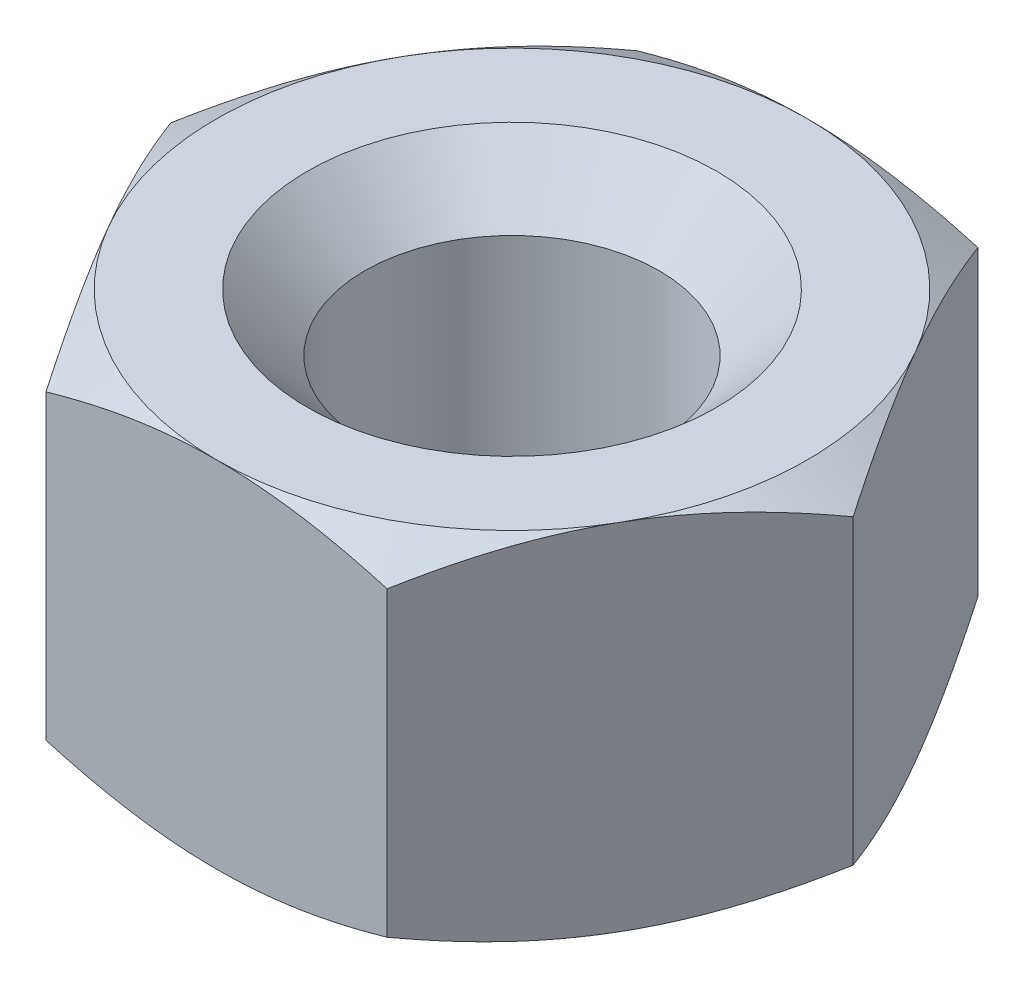
SolidWorks part; units mm, degrees
ref_plane "Plan1" through (0, 0, 0) normal (0, 0, 1) x (1, 0, 0)
ref_plane "Plan2" through (0, 0, 0) normal (0, 1, 0) x (1, 0, 0)
ref_plane "Plan3" through (0, 0, 0) normal (1, 0, 0) x (0, 0, -1)
sketch "Esquisse1" plane through (0, 0, 0) normal (0, 0, 1) x (1, 0, 0)
  line L1 (4.4845, 10.8) -> (9, 10.8)
  line L2 (9, 10.8) -> (12.7279, 8.6477)
  line L3 (12.7279, 8.6477) -> (12.7279, 2.1523)
  line L4 (12.7279, 2.1523) -> (9, 0)
  line L5 (9, 0) -> (4.4845, 0)
  line L6 (0, 2.4) -> (0, 0) construction
  line L7 (4.4845, 0) -> (4.4845, 10.8)
  line L8 (-2.75, 0) -> (15.25, 0) construction
  line L9 (-1.5155, 0) -> (10.4845, 0) construction
  dimension "D1" = 12.7279
  dimension "Hauteur" = 10.8
  dimension "D2" = 30
  dimension "D4" = 9
  dimension "D5" = 30
  dimension "D6" = 4.4845
  dimension "Cote sur plats" = 18
  dimension "Diamètre nominal" = 12
revolve "Base-Révolution" add sketch "Esquisse1" angle 360 about L6
sketch "Esquisse2" plane through (0, 0, 0) normal (0, 1, 0) x (1, 0, 0)
  line L0 (0, 2.4733) -> (0, -2.457) construction
  line L1 (0, 0) -> (1.6745, -2.9003) construction
  line L2 (-5.1962, -9) -> (5.1962, -9)
  line L3 (0, 0) -> (2.3797, -1.3739) construction
  line L4 (5.1962, -9) -> (10.3923, 0)
  line L5 (0, 0) -> (2.9763, 0) construction
  line L6 (5.1962, 9) -> (10.3923, 0)
  line L7 (-5.1962, 9) -> (5.1962, 9)
  line L8 (-5.1962, 9) -> (-10.3923, 0)
  line L9 (-5.1962, -9) -> (-10.3923, 0)
  circle A0 centre (0, 0) radius 9 construction
  point P14 (0, 9)
  point P16 (0, -9)
  dimension "D1" = 30
  dimension "D2" = 30
extrude "Enlèv. mat.-Extru.1" cut sketch "Esquisse2" along normal blind 10.8 flip side to cut
chamfer "Chanfrein" distance 1.75 angle 45 2 edges at (0, 10.8, 4.4845) (0, 0, 4.4845)
sketch "Cercle-Filetage3D" plane through (0, 0, 0) normal (0, 1, 0) x (-1, 0, 0)
  circle A0 centre (0, 0) radius 6
  dimension "Diamètre nominal" = 12
curve "Hélice1" pitch 1.75 height 10.8 turns 6.1714 parameters "Pas"=1.75
sketch "Outil-Filetage3D" plane through (0, 0, 0) normal (0, 0, 1) x (1, 0, 0)
  line L0 (6, 0) -> (4.4616, 0.8704)
  line L1 (0, 0) -> (0, 2.4) construction
  line L2 (0, 10.8) -> (0, 9.05) construction
  line L3 (0, 0) -> (7.7942, 0) construction
  line L4 (3.5866, 0.4375) -> (3.5866, -0.4375)
  line L6 (4.4616, 0.8704) -> (4.4616, 0.4375)
  line L7 (4.4616, 0.4375) -> (3.5866, 0.4375)
  line L10 (6, 0) -> (3.5866, 0) construction
  line L11 (4.4769, 0.8617) -> (4.4769, -0.2462) construction
  line L12 (4.4616, -0.4375) -> (3.5866, -0.4375)
  line L13 (4.4616, -0.8704) -> (4.4616, -0.4375)
  line L14 (6, 0) -> (4.4616, -0.8704)
  dimension "D1" = 1.7675
  dimension "D2" = 29.5
  dimension "D3" = 6
  dimension "Pas" = 1.75
  dimension "D4" = 0.875
  dimension "D5" = 0.875
sweep "Filetage3D" [suppressed] cut profiles "Outil-Filetage3D" path "Hélice1"
equation "\"D4@Esquisse1\" = \"Cote sur plats@Esquisse1\"/2"
equation "\"D1@Esquisse1\" =(\"D4@Esquisse1\"*sqr(2)*2)/2"
equation "\"D1@Enlèv. mat.-Extru.1\" = \"Hauteur@Esquisse1\""
equation "\"D3@Hélice1\" = \"Hauteur@Esquisse1\""
equation "\"D5@Hélice1\" = \"D3@Hélice1\"/\"Pas@Hélice1\""
equation "\"D6@Esquisse1\" = (\"Diamètre nominal@Esquisse1\"/2)-(\"Pas@Chanfrein\"*sqr(3)/2)"
equation "\"D5@Outil-Filetage3D\" = \"Pas@Outil-Filetage3D\"/2"
equation "\"D4@Outil-Filetage3D\" = \"Pas@Outil-Filetage3D\"/2"
equation "\"D1@Outil-Filetage3D\" = \"Pas@Outil-Filetage3D\"+(\"Pas@Outil-Filetage3D\"/100)"
equation "\"D3@Outil-Filetage3D\" = \"Diamètre nominal@Esquisse1\"/2"
